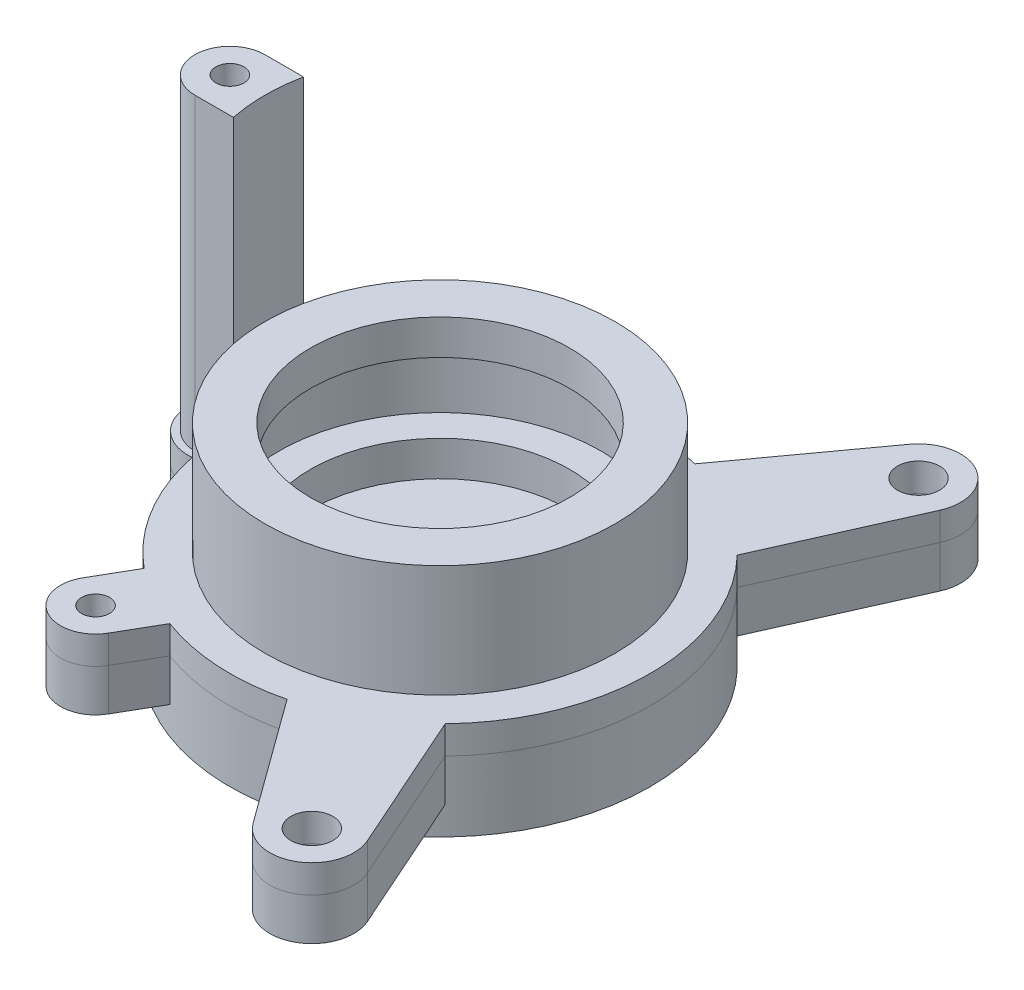
SolidWorks part; units mm, degrees
ref_plane "Front Plane" through (0, 0, 0) normal (0, 0, 1) x (1, 0, 0)
ref_plane "Top Plane" through (0, 0, 0) normal (0, 1, 0) x (1, 0, 0)
ref_plane "Right Plane" through (0, 0, 0) normal (1, 0, 0) x (0, 0, -1)
sketch "Sketch1" plane through (0, 0, 0) normal (0, 1, 0) x (1, 0, 0)
  circle A0 centre (0, 0) radius 9 construction
  circle A1 centre (0, 0) radius 12 construction
  circle A2 centre (0, 0) radius 9.25
  circle A3 centre (0, 0) radius 11.5
  circle A4 centre (0, 0) radius 12.5
  dimension "D1" = 18
  dimension "D2" = 24
  dimension "D3" = 18.5
  dimension "D4" = 23
  dimension "D5" = 25
extrude "Boss-Extrude1" add sketch "Sketch1" along normal blind 10 contours A4 A3 | A3 A2 region at (-11.1747, 0, 0) region at (-12.1464, 0, 0)
ref_plane "Plane1" through (0, 7.5, 0) normal (0, 1, 0) x (1, 0, 0)
sketch "Sketch2" plane through (0, 7.5, 0) normal (0, 1, 0) x (1, 0, 0)
  circle A0 centre (0, 0) radius 9.25
  circle A1 centre (0, 0) radius 11.5
  dimension "D1" = 18.5
  dimension "D2" = 23
extrude "Cut-Extrude1" cut sketch "Sketch2" against normal blind 5
sketch "Sketch3" plane through (0, 0, 0) normal (0, -1, 0) x (1, 0, 0)
  line L0 (0, 0) -> (-15, 0) construction
  circle A0 centre (0, 0) radius 15
  circle A1 centre (-15, 0) radius 3
  circle M2 centre (0, 0) radius 12.5
  circle M3 centre (0, 0) radius 9.25
  dimension "D1" = 30
  dimension "D3" = 6
  dimension "D2" = 15
extrude "Boss-Extrude2" add sketch "Sketch3" along normal blind 5 and the other way blind 2 contours A1 A0 M2 | L0 A1 A0 M2 | L0 A0 A1 M2 | A1 M3 M2 | M3 | L0 A1 M2 | A1 L0 M2 | A0 A1 region at (-11.7632, 0, 0.8747) region at (-12.2805, 0, -0.5712) region at (-12.2805, 0, 0.5712) region at (0, 0, 8.9884) region at (-13.7878, 0, -1.2837) region at (-13.7878, 0, 1.2837) region at (-13.1488, 0, 2.8782) region at (-16.2177, 0, 0)
sketch "Sketch4" plane through (0, 2, 0) normal (0, 1, 0) x (1, 0, 0)
  line L0 (0, 0) -> (-15, 0) construction
  line L1 (-15, 2.5) -> (-12.2474, 2.5)
  line L2 (-15, -2.5) -> (-12.2474, -2.5)
  circle A0 centre (-15, 0) radius 2.5
  circle A1 centre (-15, 0) radius 1
  circle A2 centre (0, 0) radius 12.5 construction
  circle M2 centre (0, 0) radius 12.5
  dimension "D2" = 5
  dimension "D3" = 2
  dimension "D1" = 15
extrude "Boss-Extrude4" add sketch "Sketch4" along normal blind 22 contours A0 A1 | A0 L1 M2 | A0 L2 M2 region at (-12.9727, 2, -1.9328) region at (-13.2822, 2, -1.7178) region at (-12.9727, 2, 1.9328)
extrude "Cut-Extrude8" cut sketch "Sketch4<3>" against normal blind 2 contours A1 region at (-15, 2, 0)
sketch "Sketch4<3>" plane through (0, 2, 0) normal (0, 1, 0) x (1, 0, 0) same geometry as "Sketch4"
sketch "Sketch5" plane through (0, 0, 0) normal (0, 1, 0) x (1, 0, 0)
  line L0 (0, 0) -> (-9, 15.5885) construction
  line L1 (0, 0) -> (18, 0) construction
  line L2 (-11.1651, 14.3385) -> (-8.2888, 9.3566)
  line L3 (-6.8349, 16.8385) -> (-3.9587, 11.8566)
  line L4 (0, 0) -> (12.5, 21.6506) construction
  line L5 (10.0729, 23.414) -> (2.0237, 12.3351)
  line L6 (15.2406, 20.4304) -> (9.6707, 7.9201)
  line L7 (2.0237, 12.3351) -> (9.6707, 7.9201)
  circle A0 centre (0, 0) radius 18 construction
  circle A1 centre (-9, 15.5885) radius 2.5
  circle A2 centre (0, 0) radius 12.5 construction
  circle A3 centre (-9, 15.5885) radius 1.6 construction
  circle A4 centre (-9, 15.5885) radius 1
  arc A5 (-8.2888, 9.3566) -> (-3.9587, 11.8566) centre (0, 0) cw
  circle A6 centre (12.5, 21.6506) radius 3
  circle A7 centre (12.5, 21.6506) radius 2.1 construction
  circle A8 centre (12.5, 21.6506) radius 1.5
  point P21 (0, 0)
  point P22 (0, 0)
  point P23 (0, 0)
  point P24 (9.1687, 21.0007)
  point P25 (10.2991, 22.8365)
  point P26 (14.8726, 20.8626)
  dimension "D1" = 36
  dimension "D4" = 25
  dimension "D5" = 5
  dimension "D6" = 3.2
  dimension "D7" = 2
  dimension "D10" = 6
  dimension "D11" = 4.2
  dimension "D12" = 3
  dimension "D2" = 18
  dimension "D3" = 120
  dimension "D8" = 60
  dimension "D9" = 25
  dimension "D13" = 6
  dimension "D14" = 6
extrude "ARMS" add sketch "Sketch5" along normal blind 2 and the other way blind 3 contours L2 A5 A1 | A1 A5 A3 | A5 A1 | A1 A5 L3 | A3 A4 | A6 A8 | A6 L5 L7 L6 region at (-7.1343, 0, -12.3569) region at (-10.2146, 0, -17.6923) region at (8.4816, 0, -14.6905) region at (13.4008, 0, -24.4231)
sketch "Sketch7" plane through (0, -5, 0) normal (0, -1, 0) x (1, 0, 0)
  line L0 (0, 0) -> (-9, -15.5885) construction
  line L1 (0, 0) -> (12.5, -21.6506) construction
  circle A0 centre (-9, -15.5885) radius 1.6
  circle A1 centre (12.5, -21.6506) radius 2.1
  dimension "D1" = 3.2
  dimension "D2" = 4.2
extrude "Cut-Extrude4" cut sketch "Sketch7" against normal blind 4
mirror "Mirror1" about plane through (0, 0, 0) normal (0, 0, 1) of "Cut-Extrude4", "ARMS"
sketch "Sketch9" plane through (0, 0, 0) normal (0, 1, 0) x (1, 0, 0)
  line L0 (-15, 0) -> (-14, 0) construction
  circle A0 centre (0, 0) radius 14
  circle A1 centre (-9, 15.5885) radius 2
  circle A2 centre (-9, -15.5885) radius 2
  circle A3 centre (-15, 0) radius 1.5
  arc A4 (-15.2679, 1.4759) -> (-13.6719, 3.0133) centre (-15.625, 3.4437) ccw
  arc A5 (-15.2679, -1.4759) -> (-13.6719, -3.0133) centre (-15.625, -3.4437) cw
  dimension "D1" = 28
  dimension "D2" = 4
  dimension "D3" = 4
  dimension "D4" = 3
  dimension "D5" = 2
extrude "Cut-Extrude6" cut sketch "Sketch9" against normal blind 3 contours A3 A0 A2 A1 | A4 A3 A0 | A0 A3 | A3 A5 A0 | A0 A3 region at (0.0167, 0, 0) region at (-14.1988, 0, -1.7328) region at (-14.1988, 0, 1.7328) region at (-13.7887, 0, 0) region at (-15.1422, 0, 0)
sketch "Sketch10" plane through (0, 2, 0) normal (0, 1, 0) x (1, 0, 0)
  circle A0 centre (0, 0) radius 9.25
  dimension "D1" = 18.5
extrude "Cut-Extrude7" cut sketch "Sketch10" against normal blind 2
split "Split1" trim tools "Top Plane" bodies to split 114 resulting bodies 111 112
